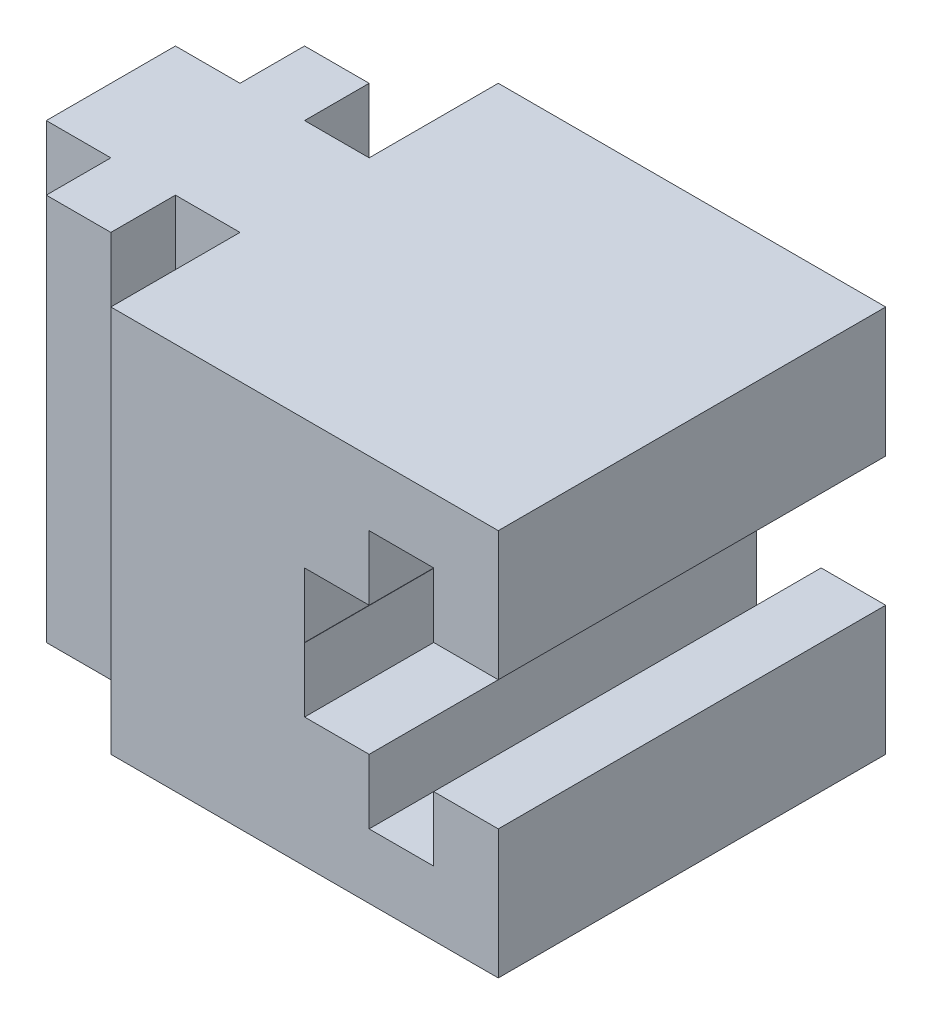
SolidWorks part; units mm, degrees
note: '?' marks a value the reader was unsure of.
ref_plane "Front Plane" through (0, 0, 0) normal (0, 0, 1) x (1, 0, 0)
ref_plane "Top Plane" through (0, 0, 0) normal (0, 1, 0) x (1, 0, 0)
ref_plane "Right Plane" through (0, 0, 0) normal (1, 0, 0) x (0, 0, -1)
other "Center of Mass"
sketch "Sketch2" plane through (0, 0, 0) normal (1, 0, 0) x (0, 0, -1)
  line L1 (-75, 75) -> (75, 75)
  line L2 (-75, 75) -> (-75, -75)
  line L3 (-75, -75) -> (75, -75)
  line L4 (75, 75) -> (75, -75)
  line L5 (-75, 75) -> (75, -75) construction
  line L6 (-75, -75) -> (75, 75) construction
  point P0 (0, 0)
  dimension "D1" = 150
  dimension "D2" = 150
extrude "Boss-Extrude1" add sketch "Sketch2" along normal blind 225
sketch "Sketch3" plane through (0, 75, 0) normal (0, 1, 0) x (1, 0, 0)
  line L1 (0, 75) -> (0, -75) construction
  line L2 (0, 25) -> (25, 25)
  line L3 (25, 25) -> (25, 50)
  line L4 (25, 50) -> (50, 50)
  line L5 (50, 50) -> (50, 25)
  line L6 (50, 25) -> (75, 25)
  line L8 (75, -25) -> (50, -25)
  line L9 (50, -25) -> (50, -50)
  line L11 (25, -50) -> (25, -25)
  line L12 (25, -25) -> (0, -25)
  line L14 (75, 25) -> (75, 75)
  line L17 (75, 75) -> (0, 75)
  line L18 (225, 75) -> (0, 75) construction
  line L19 (0, 75) -> (0, 25)
  line L20 (0, -25) -> (0, -75)
  line L21 (25, -50) -> (50, -50)
  line L23 (0, -75) -> (75, -75)
  line L24 (225, -75) -> (0, -75) construction
  line L27 (75, -75) -> (75, -25)
  dimension "D1" = 50
  dimension "D2" = 75
  dimension "D3" = 50
  dimension "D4" = 75
  dimension "D5" = 25
  dimension "D6" = 25
  dimension "D7" = 25
  dimension "D8" = 25
  dimension "D9" = 25
  dimension "D10" = 25
  dimension "D11" = 25
  dimension "D12" = 25
extrude "Cut-Extrude1" cut sketch "Sketch3" against normal blind 150
sketch "Sketch4" plane through (0, 0, 75) normal (0, 0, 1) x (1, 0, 0)
  line L0 (225, 25) -> (200, 25)
  line L1 (225, 75) -> (225, -75) construction
  line L2 (200, 25) -> (200, 50)
  line L3 (200, 50) -> (175, 50)
  line L4 (175, 50) -> (175, 25)
  line L5 (175, 25) -> (150, 25)
  line L6 (150, 25) -> (150, 0)
  line L7 (150, -25) -> (175, -25)
  line L8 (175, -25) -> (175, -50)
  line L9 (175, -50) -> (200, -50)
  line L10 (200, -50) -> (200, -25)
  line L11 (200, -25) -> (225, -25)
  line L12 (225, -25) -> (225, 25)
  line L13 (225, 75) -> (75, 75) construction
  line L14 (150, -0.1271) -> (150, -25)
  line L15 (150, 0) -> (149.8568, 0)
  line L17 (150, -0.1271) -> (149.8568, -0.1271)
  line L18 (149.8568, 0) -> (149.8568, -0.1271)
  dimension "D1" = 50
  dimension "D2" = 25
  dimension "D3" = 75
  dimension "D4" = 25
  dimension "D5" = 25
  dimension "D6" = 25
  dimension "D7" = 25
  dimension "D8" = 25
  dimension "D9" = 25
  dimension "D10" = 25
  dimension "D11" = 25
extrude "Cut-Extrude2" cut sketch "Sketch4" against normal blind 150 contours L12 L0 L2 L3 L4 L5 L6 L15 L18 L17 L14 L7 L8 L9 L10 L11
ref_plane "Plane7" through (37.5, 0, 0) normal (-1, 0, 0) x (0, 0, 1)
ref_plane "Plane8" through (0, 0, 0) normal (0, 0, -1) x (-1, 0, 0)
ref_axis "Link_2_1_Axis" through (37.5, -82.5, 0) along (0, 1, 0)?
ref_plane "Plane9" through (0, 0, 0) normal (0, -1, 0) x (-1, 0, 0)
ref_plane "Plane10" through (187.5, 0, 0) normal (1, 0, 0) x (0, 0, -1)
ref_axis "Link_2_3_Axis" through (187.5, 0, -82.5) along (0, 0, 1)?
